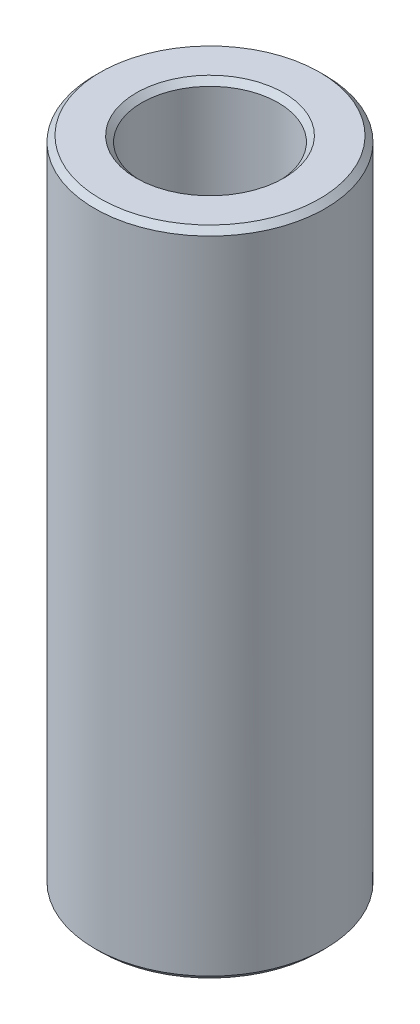
SolidWorks part; units mm, degrees
ref_plane "Front Plane" through (0, 0, 0) normal (0, 0, 1) x (1, 0, 0)
ref_plane "Top Plane" through (0, 0, 0) normal (0, 1, 0) x (1, 0, 0)
ref_plane "Right Plane" through (0, 0, 0) normal (1, 0, 0) x (0, 0, -1)
sketch "Sketch1" plane through (0, 0, 0) normal (0, 1, 0) x (1, 0, 0)
  circle A0 centre (0, 0) radius 37.5
  dimension "SLEEVE_OD" = 75
extrude "Boss-Extrude1" add sketch "Sketch1" along normal blind 212.1306
sketch "Sketch2" plane through (0, 0, 0) normal (0, 1, 0) x (1, 0, 0)
  circle A0 centre (0, 0) radius 22.1865
  dimension "BORE_D" = 44.373
extrude "Cut-Extrude1" cut sketch "Sketch2" along normal through all
chamfer "Chamfer1" distance 1.8363 angle 45 4 edges at (0, 212.1306, 22.1865) (0, 0, 22.1865) (0, 0, 37.5) (0, 212.1306, 37.5)
